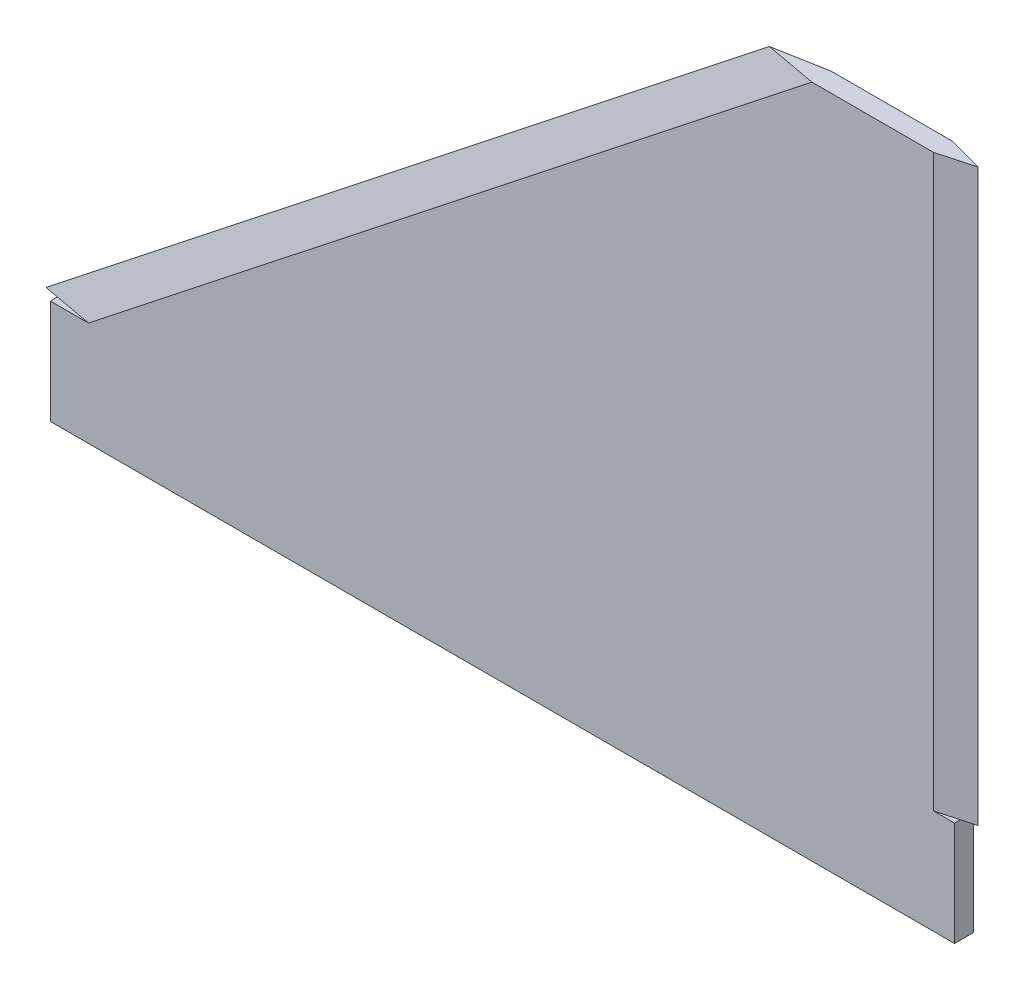
SolidWorks part; units mm, degrees
material "Hexcel AS4C (3000 Filaments)"
ref_plane "Front Plane" through (0, 0, 0) normal (0, 0, 1) x (1, 0, 0)
ref_plane "Top Plane" through (0, 0, 0) normal (0, 1, 0) x (1, 0, 0)
ref_plane "Right Plane" through (0, 0, 0) normal (1, 0, 0) x (0, 0, -1)
sketch "Sketch1" plane through (0, 0, 0) normal (0, 0, 1) x (1, 0, 0)
  line L0 (-130, 0) -> (-134, 0)
  line L1 (-130, -30) -> (130, -30)
  line L2 (-130, -30) -> (-130, 0)
  line L4 (130, -30) -> (130, 0)
  line L5 (-134, 0) -> (74, 164)
  line L6 (74, 164) -> (134, 164)
  line L7 (134, 164) -> (134, 0)
  line L8 (134, 0) -> (130, 0)
  line L9 (-130, 0) -> (130, 0)
  dimension "D1" = 30
  dimension "D2" = 268
  dimension "D3" = 260
  dimension "D4" = 164
  dimension "D5" = 60
extrude "Boss-Extrude1" add sketch "Sketch1" along normal blind 2.75 and the other way blind 2.75 contours L9 L2 L1 L4 | L0 L9 L8 L7 L6 L5 region at (0, -15, 0) region at (41.0081, 64.6667, 0)
sketch "Sketch2" plane through (0, 164, 0) normal (0, 1, 0) x (1, 0, 0)
  line L0 (74, 0) -> (89, -2.75)
  line L1 (74, 2.75) -> (74, -2.75) construction
  line L2 (74, -2.75) -> (134, -2.75) construction
  line L3 (89, -2.75) -> (74, -2.75)
  line L4 (74, -2.75) -> (74, 0)
  line L5 (74, 2.75) -> (74, 0)
  line L6 (89, 2.75) -> (74, 0)
  line L7 (74, 2.75) -> (134, 2.75) construction
  line L8 (74, 2.75) -> (89, 2.75)
  line L9 (89, 2.75) -> (89, -2.75) construction
  line M3 (74, 2.75) -> (74, -2.75)
  line M4 (74, -2.75) -> (134, -2.75)
  line M6 (134, 2.75) -> (74, 2.75)
  dimension "D1" = 15
extrude "Cut-Extrude1" cut sketch "Sketch2" along direction (0.7853, 0.6192, 0) on the side against the normal up to surface (164 mm away) contours L0 M3 M4 | L6 M6 M3 region at (79, 164, 1.8333) region at (79, 164, -1.8333) up to face at (132, 0, 0)
sketch "Sketch3" plane through (0, 164, 0) normal (0, 1, 0) x (1, 0, 0)
  line L0 (124, 2.75) -> (134, 2.75)
  line L1 (89, 2.75) -> (134, 2.75) construction
  line L2 (134, -2.75) -> (134, 0)
  line L3 (134, -2.75) -> (124, -2.75)
  line L4 (89, -2.75) -> (134, -2.75) construction
  line L5 (124, -2.75) -> (134, 0)
  line L6 (134, 0) -> (124, 2.75)
  line L7 (124, 2.75) -> (124, -2.75) construction
  line L8 (134, 2.75) -> (134, 0)
  line M5 (89, -2.75) -> (134, -2.75)
  line M6 (134, -2.75) -> (134, 2.75)
  line M7 (134, 2.75) -> (89, 2.75)
  dimension "D1" = 10
extrude "Cut-Extrude2" cut sketch "Sketch3" against normal up to surface (164 mm away) contours L5 M5 M6 | L6 M6 M7 region at (130.6667, 164, 1.8333) region at (130.6667, 164, -1.8333) up to face at (132, 0, 0)
